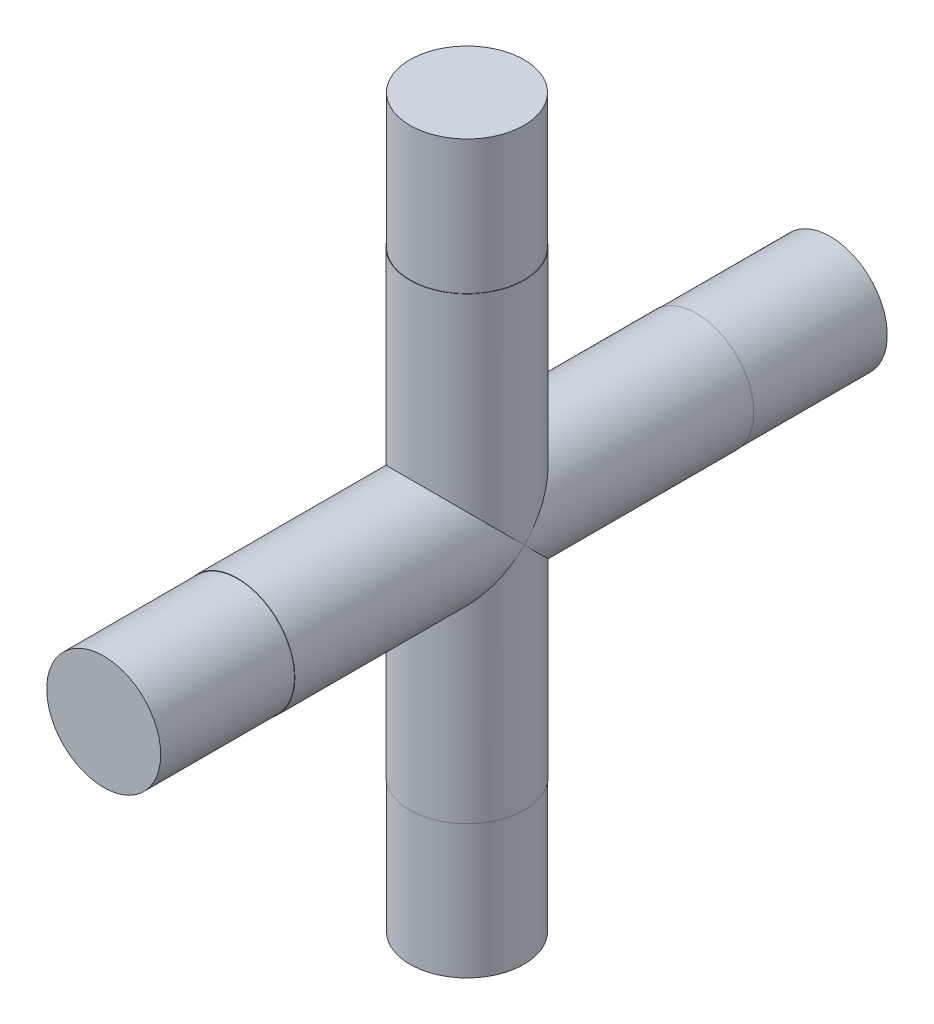
SolidWorks part; units mm, degrees
material "AISI 1020"
ref_plane "Front Plane" through (0, 0, 0) normal (0, 0, 1) x (1, 0, 0)
ref_plane "Top Plane" through (0, 0, 0) normal (0, 1, 0) x (1, 0, 0)
ref_plane "Right Plane" through (0, 0, 0) normal (1, 0, 0) x (0, 0, -1)
sketch "Sketch1" plane through (0, 0, 0) normal (0, 1, 0) x (1, 0, 0)
  circle A0 centre (0, 0) radius 1.5
extrude "Boss-Extrude1" add sketch "Sketch1" along normal blind 19
sketch "Sketch2" plane through (0, 0, 0) normal (0, 0, 1) x (1, 0, 0)
  line L0 (0, 0) -> (0, 19) construction
  line L1 (1.5, 19) -> (-1.5, 19) construction
  circle A0 centre (0, 9.5) radius 1.5
extrude "Boss-Extrude2" add sketch "Sketch2" along normal blind 9.5 and the other way blind 9.5
sketch "Sketch3" plane through (0, 0, -9.5) normal (0, 0, -1) x (-1, 0, 0)
  circle A0 centre (0, 9.5) radius 1.49
  circle A1 centre (0, 9.5) radius 1.5
extrude "Cut-Extrude1" cut sketch "Sketch3" against normal blind 3.5
sketch "Sketch4" plane through (0, 0, 9.5) normal (0, 0, 1) x (1, 0, 0)
  circle A0 centre (0, 9.5) radius 1.49
  circle A1 centre (0, 9.5) radius 1.5
extrude "Cut-Extrude2" cut sketch "Sketch4" against normal blind 3.5
sketch "Sketch5" plane through (0, 19, 0) normal (0, 1, 0) x (1, 0, 0)
  circle A0 centre (0, 0) radius 1.49
  circle A1 centre (0, 0) radius 1.5
extrude "Cut-Extrude3" cut sketch "Sketch5" against normal blind 3.5
sketch "Sketch6" plane through (0, 0, 0) normal (0, -1, 0) x (1, 0, 0)
  circle A0 centre (0, 0) radius 1.49
  circle A1 centre (0, 0) radius 1.5
extrude "Cut-Extrude4" cut sketch "Sketch6" against normal blind 3.5
